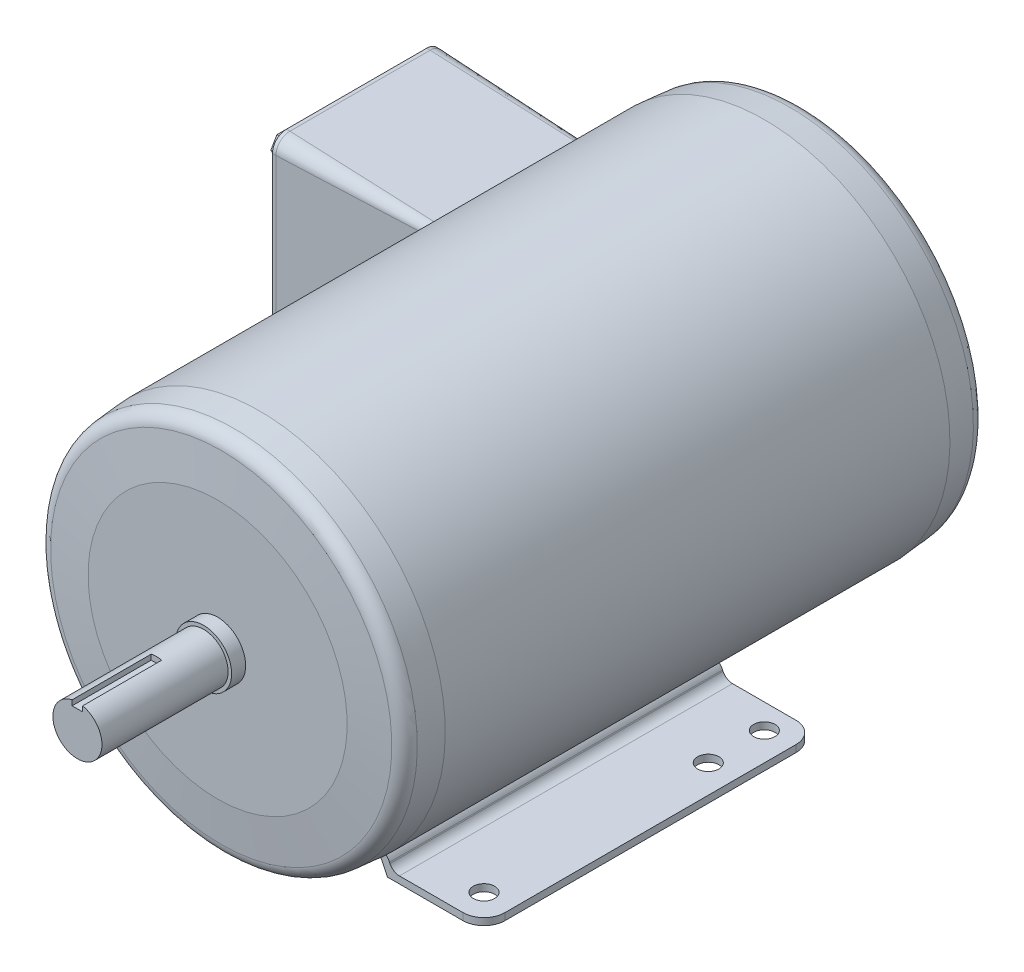
SolidWorks part; units mm, degrees
ref_plane "Front Plane" through (0, 0, 0) normal (0, 0, 1) x (1, 0, 0)
ref_plane "Top Plane" through (0, 0, 0) normal (0, 1, 0) x (1, 0, 0)
ref_plane "Right Plane" through (0, 0, 0) normal (1, 0, 0) x (0, 0, -1)
sketch "Sketch1" plane through (0, 0, 0) normal (0, 0, 1) x (1, 0, 0)
  line L0 (-82.55, -88.9) -> (-38.1, -88.9)
  line L1 (-38.1, -88.9) -> (-38.1, -85.725)
  line L2 (-38.1, -85.725) -> (-82.55, -85.725)
  line L3 (-82.55, -85.725) -> (-82.55, -88.9)
  line L4 (0, 0) -> (0, -88.9) construction
  line L5 (82.55, -85.725) -> (82.55, -88.9)
  line L6 (38.1, -85.725) -> (82.55, -85.725)
  line L7 (38.1, -88.9) -> (38.1, -85.725)
  line L8 (82.55, -88.9) -> (38.1, -88.9)
  line L9 (-69.85, -88.9) -> (-69.85, -85.725) construction
  line L10 (69.85, -88.9) -> (69.85, -85.725) construction
  line L11 (0, 0) -> (0, 84.074) construction
  line L12 (-2.3876, 8.4709) -> (2.3876, 8.4709) construction
  line L13 (-2.3876, 8.4709) -> (-2.3876, 10.853) construction
  line L14 (2.3876, 8.4709) -> (2.3876, 10.853) construction
  line L15 (0, 0) -> (84.074, 0) construction
  line L16 (0, 0) -> (-142.494, 0) construction
  line L17 (-142.494, 50.8) -> (-142.494, -50.8) construction
  line L18 (-142.494, 0) -> (-115.824, 0) construction
  line L19 (-115.824, 0) -> (-115.824, -50.8) construction
  line L20 (-142.494, -50.8) -> (-89.154, -50.8) construction
  line L22 (0, 0) -> (84.074, 0) construction
  line L23 (84.074, 12.7) -> (84.074, -25.4) construction
  circle A0 centre (0, 0) radius 84.074
  circle A1 centre (0, 0) radius 11.1125
  point P19 (0, 11.1125)
  dimension "D1" = 25.4
  dimension "P" = 168.148
  dimension "U" = 22.225
  dimension "A" = 165.1
  dimension "D" = 88.9
  dimension "E" = 69.85
  dimension "2E" = 139.7
  dimension "G" = 3.175
  dimension "J" = 44.45
  dimension "O" = 172.974
  dimension "R" = 19.5834
  dimension "S" = 4.7752
  dimension "U-R" = 2.6416
  dimension "AB" = 142.494
  dimension "AE" = 88.9
  dimension "AF" = 50.8
  dimension "AC" = 115.824
  dimension "OL" = 84.074
  dimension "D2" = 12.7
sketch "Sketch2" plane through (0, 0, 0) normal (1, 0, 0) x (0, 0, -1)
  line L0 (0, 0) -> (330.2, 0) construction
  line L1 (101.6, -88.9) -> (252.476, -88.9) construction
  line L3 (252.476, -85.725) -> (101.6, -85.725) construction
  line L4 (101.6, -88.9) -> (127, -88.9)
  line L5 (101.6, -88.9) -> (101.6, -85.725)
  line L6 (101.6, -85.725) -> (127, -85.725)
  line L7 (127, -88.9) -> (127, -85.725)
  line L8 (203.2, -88.9) -> (203.2, -85.725)
  line L9 (252.476, -88.9) -> (203.2, -88.9)
  line L10 (252.476, -85.725) -> (203.2, -85.725)
  line L11 (252.476, -88.9) -> (252.476, -85.725)
  line L12 (114.3, -88.9) -> (114.3, -85.725) construction
  line L13 (215.9, -88.9) -> (215.9, -85.725) construction
  line L14 (109.474, -88.9) -> (109.474, -85.725) construction
  line L15 (119.126, -88.9) -> (119.126, -85.725) construction
  line L16 (0, 11.1125) -> (0, 0) construction
  line L18 (241.3, -88.9) -> (241.3, -85.725) construction
  line L19 (165.1, 0) -> (165.1, -88.9) construction
  line L20 (203.2, -88.9) -> (127, -88.9) construction
  point P5 (35.814, 0)
  point P7 (264.16, 0)
  point P23 (63.5, 0)
  point P24 (57.15, 0)
  point P25 (50.8, 0)
  dimension "D1" = 66.04
  dimension "B" = 150.876
  dimension "C" = 330.2
  dimension "2F" = 101.6
  dimension "H" = 9.652
  dimension "K" = 25.4
  dimension "N" = 63.5
  dimension "W" = 6.35
  dimension "N-W" = 57.15
  dimension "V" = 50.8
  dimension "BA" = 57.15
  dimension "ES" = 35.814
  dimension "BS" = 149.86
  dimension "EV" = 12.7
  dimension "D5" = 12.7
  dimension "D6" = 127
sketch "Sketch3" plane through (0, 0, 0) normal (1, 0, 0) x (0, 0, -1)
  line L0 (0, 0) -> (330.2, 0) construction
  line L1 (82.55, 0) -> (311.15, 0)
  line L2 (82.55, 0) -> (82.55, 84.074) construction
  line L3 (82.55, 84.074) -> (311.15, 84.074)
  line L4 (311.15, 0) -> (311.15, 84.074) construction
  line L5 (82.55, 84.074) -> (70.9004, 83.0548)
  line L6 (65.128, 77.2824) -> (63.5, 58.674)
  line L7 (196.85, 84.074) -> (196.85, 0) construction
  line L8 (330.2, 0) -> (330.2, 58.674)
  line L9 (311.15, 84.074) -> (322.7996, 83.0548)
  line L10 (82.55, 0) -> (63.5, 0)
  line L11 (311.15, 0) -> (330.2, 0)
  line L12 (63.5, 0) -> (63.5, 58.674)
  line L13 (328.572, 77.2824) -> (330.2, 58.674)
  line L14 (0, 0) -> (63.5, 0) construction
  arc A0 (70.9004, 83.0548) -> (65.128, 77.2824) centre (71.4539, 76.729) ccw
  arc A1 (322.7996, 83.0548) -> (328.572, 77.2824) centre (322.2461, 76.729) cw
  dimension "D3" = 6.35
  dimension "D1" = 5
  dimension "D2" = 19.05
  dimension "D4" = 5
  dimension "D5" = 25.4
revolve "Revolve1" add sketch "Sketch3" angle 360 about L1
sketch "Sketch4" plane through (0, 0, 0) normal (1, 0, 0) x (0, 0, -1)
  line L0 (57.15, 11.1125) -> (57.15, 12.7)
  line L1 (0, 0) -> (63.5, 0)
  line L2 (0, 0) -> (0, 11.1125)
  line L3 (0, 11.1125) -> (57.15, 11.1125)
  line L4 (63.5, 0) -> (63.5, 12.7)
  line L5 (57.15, 12.7) -> (63.5, 12.7)
  line L6 (63.5, 58.674) -> (63.5, -58.674) construction
  line L7 (57.15, 11.1125) -> (57.15, 0) construction
  line L8 (12.7, 11.1125) -> (12.7, 0) construction
  dimension "D1" = 1.5875
  dimension "D2" = 12.7
revolve "Revolve2" add sketch "Sketch4" angle 360 about L1
sketch "Sketch5" plane through (0, 0, 0) normal (0, 0, 1) x (1, 0, 0)
  line L1 (-2.3876, 13.2461) -> (2.3876, 13.2461)
  line L2 (-2.3876, 13.2461) -> (-2.3876, 8.4709)
  line L3 (-2.3876, 8.4709) -> (2.3876, 8.4709)
  line L4 (2.3876, 13.2461) -> (2.3876, 8.4709)
extrude "Cut-Extrude1" cut sketch "Sketch5" against normal up to vertex (35.814 mm away) up to point (0, 0, -35.814)
ref_plane "Plane1" through (0, -88.9, 0) normal (0, 1, 0) x (-1, 0, 0)
sketch "Sketch6" plane through (0, -88.9, 0) normal (0, 1, 0) x (-1, 0, 0)
  line L0 (0, 0) -> (0, -330.2) construction
  line L1 (73.025, -101.6) -> (38.1, -101.6)
  line L2 (82.55, -111.125) -> (82.55, -242.951)
  line L3 (-73.025, -252.476) -> (-38.1, -252.476)
  line L4 (38.1, -101.6) -> (38.1, -252.476)
  line L5 (-38.1, -101.6) -> (-38.1, -252.476)
  line L6 (-82.55, -111.125) -> (-82.55, -242.951)
  line L7 (73.025, -252.476) -> (38.1, -252.476)
  line L8 (-73.025, -101.6) -> (-38.1, -101.6)
  line L9 (-58.674, -330.2) -> (58.674, -330.2) construction
  line L10 (69.85, -114.3) -> (69.85, -215.9) construction
  line L11 (69.85, -215.9) -> (69.85, -241.3) construction
  arc A0 (-82.55, -242.951) -> (-73.025, -252.476) centre (-73.025, -242.951) ccw
  arc A1 (-73.025, -101.6) -> (-82.55, -111.125) centre (-73.025, -111.125) ccw
  circle A2 centre (69.85, -114.3) radius 4.826
  circle A4 centre (69.85, -215.9) radius 4.826
  circle A5 centre (69.85, -241.3) radius 4.826
  circle A6 centre (-69.85, -241.3) radius 4.826
  circle A7 centre (-69.85, -215.9) radius 4.826
  arc A8 (73.025, -101.6) -> (82.55, -111.125) centre (73.025, -111.125) cw
  circle A9 centre (-69.85, -114.3) radius 4.826
  arc A11 (82.55, -242.951) -> (73.025, -252.476) centre (73.025, -242.951) cw
  point P30 (69.85, -109.474)
  dimension "D2" = 9.525
extrude "Boss-Extrude1" add sketch "Sketch6" along normal up to vertex (3.175 mm away) separate body up to point (-82.55, -85.725, 0)
sketch "Sketch7" plane through (0, -85.725, 0) normal (0, 1, 0) x (1, 0, 0)
  line L0 (38.1, 252.476) -> (38.1, 101.6) construction
  line L9 (0, 0) -> (0, 101.6) construction
  line L10 (0, 0) -> (0, 330.2) construction
  line L11 (-41.275, 252.476) -> (-41.275, 101.6)
  line L17 (41.275, 101.6) -> (-41.275, 101.6)
  line L19 (-41.275, 252.476) -> (41.275, 252.476)
  line L26 (41.275, 252.476) -> (41.275, 101.6)
  point P2 (-34.6506, 200.025)
  point P3 (-39.6875, 214.4395)
  point P6 (39.6875, 214.4395)
  point P8 (41.275, 212.725)
  point P12 (50.8, 203.2)
  point P14 (84.1375, 189.0395)
  point P16 (84.1375, 122.3645)
  point P18 (50.8, 127)
  point P31 (39.6875, 96.9645)
  point P32 (-39.6875, 96.9645)
  point P33 (-34.6506, 124.462)
  point P35 (-42.5881, 132.3995)
  point P36 (-84.1375, 122.3645)
  point P37 (-84.1375, 189.0395)
  point P38 (-42.5881, 192.0875)
  dimension "D2" = 3.175
extrude "Boss-Extrude2" add sketch "Sketch7" against normal blind 1.5875
ref_plane "Plane2" through (0, 0, -165.1) normal (0, 0, 1) x (1, 0, 0)
sketch "Sketch8" plane through (0, 0, -101.6) normal (0, 0, 1) x (1, 0, 0)
  line L0 (0, 0) -> (36.4726, -75.7508) construction
  line L1 (36.4726, -75.7508) -> (41.275, -85.725)
  line L2 (41.275, -85.725) -> (-41.275, -85.725)
  line L3 (0, -88.9) -> (0, 0) construction
  line L4 (-36.4726, -75.7508) -> (-41.275, -85.725)
  circle A0 centre (0, 0) radius 84.074 construction
  circle A1 centre (0, 0) radius 84.074 construction
  arc A2 (36.4726, -75.7508) -> (-36.4726, -75.7508) centre (0, 0) cw
extrude "Boss-Extrude4" add sketch "Sketch8" against normal up to surface (150.876 mm away) up to face at (0, -87.7094, -252.476)
sketch "Sketch9" plane through (0, 0, -101.6) normal (0, 0, 1) x (1, 0, 0)
  line L0 (38.8644, -88.9) -> (34.6207, -80.0862)
  line L1 (0, 0) -> (0, -87.3125) construction
  line L2 (-38.1, -87.3125) -> (38.1, -87.3125) construction
  line L3 (41.275, -85.725) -> (36.4726, -75.7508) construction
  line L4 (38.1, -88.9) -> (73.025, -88.9) construction
  line L5 (38.8644, -88.9) -> (-38.8644, -88.9)
  line L7 (-38.8644, -88.9) -> (-34.6207, -80.0862)
  arc A3 (-37.85, -78.6115) -> (37.85, -78.6115) centre (0, 0) ccw
  arc A4 (-34.6207, -80.0862) -> (34.6207, -80.0862) centre (0, 0) ccw
  dimension "D1" = 3.175
extrude "Cut-Extrude4" cut sketch "Sketch9" against normal up to surface (150.876 mm away) up to face at (2.2456, -86.0792, -252.476)
fillet "Fillet1" radius 4.7625 4 edges at (-34.6207, -80.0862, -177.038) (34.6207, -80.0862, -177.038)
fillet "Fillet3" radius 7.9375 2 edges at (36.4726, -75.7508, -177.038) (-36.4726, -75.7508, -177.038)
ref_plane "Plane3" through (-142.494, 0, 0) normal (1, 0, 0) x (0, 0, -1)
combine bodies "Combine1" operation type add bodies to combine 104 133
sketch "Sketch10" plane through (-142.494, 0, 0) normal (1, 0, 0) x (0, 0, -1)
  line L0 (264.16, -50.8) -> (264.16, 0) construction
  line L1 (295.91, 50.8) -> (232.41, 50.8)
  line L2 (302.26, 44.45) -> (302.26, -44.45)
  line L3 (295.91, -50.8) -> (232.41, -50.8)
  line L4 (226.06, 44.45) -> (226.06, -44.45)
  line L5 (264.16, -50.8) -> (264.16, 50.8) construction
  line L6 (302.26, 0) -> (226.06, 0) construction
  arc A0 (295.91, 50.8) -> (302.26, 44.45) centre (295.91, 44.45) cw
  arc A1 (232.41, 50.8) -> (226.06, 44.45) centre (232.41, 44.45) ccw
  arc A2 (232.41, -50.8) -> (226.06, -44.45) centre (232.41, -44.45) cw
  arc A3 (302.26, -44.45) -> (295.91, -50.8) centre (295.91, -44.45) cw
  dimension "D1" = 6.35
  dimension "D2" = 76.2
extrude "Boss-Extrude6" add sketch "Sketch10" along normal blind 6.35 separate body
sketch "Sketch11" plane through (-136.144, 0, 0) normal (1, 0, 0) x (0, 0, -1)
  line L4 (295.91, 50.8) -> (232.41, 50.8)
  line L5 (226.06, 44.45) -> (226.06, -44.45)
  line L6 (232.41, -50.8) -> (295.91, -50.8)
  line L7 (302.26, -44.45) -> (302.26, 44.45)
  line L8 (295.91, 50.8) -> (232.41, 50.8)
  line L9 (226.06, 44.45) -> (226.06, -44.45)
  line L10 (232.41, -50.8) -> (295.91, -50.8)
  line L11 (302.26, -44.45) -> (302.26, 44.45)
  arc A4 (302.26, 44.45) -> (295.91, 50.8) centre (295.91, 44.45) ccw
  arc A5 (232.41, 50.8) -> (226.06, 44.45) centre (232.41, 44.45) ccw
  arc A6 (226.06, -44.45) -> (232.41, -50.8) centre (232.41, -44.45) ccw
  arc A7 (295.91, -50.8) -> (302.26, -44.45) centre (295.91, -44.45) ccw
  arc A8 (302.26, 44.45) -> (295.91, 50.8) centre (295.91, 44.45) ccw
  arc A9 (232.41, 50.8) -> (226.06, 44.45) centre (232.41, 44.45) ccw
  arc A10 (226.06, -44.45) -> (232.41, -50.8) centre (232.41, -44.45) ccw
  arc A11 (295.91, -50.8) -> (302.26, -44.45) centre (295.91, -44.45) ccw
  dimension "D1" = 0
extrude "Boss-Extrude7" add sketch "Sketch11" along normal up to next draft 2.5 separate body
shell "Shell1" thickness 4.7625 removed face at (-73.0966, 0, -264.16)
sketch "Sketch12" plane through (0.4076, -44.838, 0) normal (0.0436, -0.999, 0) x (0.999, 0.0436, 0)
  line L0 (1.5486, -264.16) -> (-105.205, -264.16) construction
  line L1 (-116.381, -252.984) -> (-116.381, 0) construction
  line L2 (-105.205, -264.16) -> (-116.381, -264.16) construction
  line L3 (-116.381, -264.16) -> (-116.381, -252.984) construction
  line L4 (-116.381, -264.16) -> (-124.2836, -256.2574) construction
  circle A0 centre (-116.381, -264.16) radius 11.176
  dimension "D1" = 45
  dimension "AA" = 22.352
extrude "Cut-Extrude2" cut sketch "Sketch12" against normal up to next (4.7625 mm away)
sketch "Sketch13" plane through (-142.494, 0, 0) normal (-1, 0, 0) x (0, 0, 1)
  line L0 (-292.735, 41.275) -> (-292.735, 50.8) construction
  line L1 (-292.735, 41.275) -> (-235.585, 41.275) construction
  line L2 (-292.735, 41.275) -> (-292.735, -41.275) construction
  line L3 (-292.735, -41.275) -> (-235.585, -41.275) construction
  line L4 (-302.26, 44.45) -> (-302.26, -44.45)
  line L5 (-295.91, -50.8) -> (-232.41, -50.8)
  line L6 (-226.06, -44.45) -> (-226.06, 44.45)
  line L7 (-232.41, 50.8) -> (-295.91, 50.8)
  line L8 (-302.26, 44.45) -> (-302.26, -44.45)
  line L9 (-295.91, -50.8) -> (-232.41, -50.8)
  line L10 (-226.06, -44.45) -> (-226.06, 44.45)
  line L11 (-232.41, 50.8) -> (-295.91, 50.8)
  line L12 (-235.585, 41.275) -> (-235.585, -41.275) construction
  line L13 (-287.2357, 41.275) -> (-289.9854, 46.0375)
  line L14 (-289.9854, 46.0375) -> (-295.4846, 46.0375)
  line L15 (-295.4846, 46.0375) -> (-298.2343, 41.275)
  line L16 (-298.2343, 41.275) -> (-295.4846, 36.5125)
  line L17 (-295.4846, 36.5125) -> (-289.9854, 36.5125)
  line L18 (-289.9854, 36.5125) -> (-287.2357, 41.275)
  line L19 (-241.0843, 41.275) -> (-238.3346, 36.5125)
  line L20 (-238.3346, 36.5125) -> (-232.8354, 36.5125)
  line L21 (-232.8354, 36.5125) -> (-230.0857, 41.275)
  line L22 (-230.0857, 41.275) -> (-232.8354, 46.0375)
  line L23 (-232.8354, 46.0375) -> (-238.3346, 46.0375)
  line L24 (-238.3346, 46.0375) -> (-241.0843, 41.275)
  line L25 (-287.2357, -41.275) -> (-289.9854, -36.5125)
  line L26 (-289.9854, -36.5125) -> (-295.4846, -36.5125)
  line L27 (-295.4846, -36.5125) -> (-298.2343, -41.275)
  line L28 (-298.2343, -41.275) -> (-295.4846, -46.0375)
  line L29 (-295.4846, -46.0375) -> (-289.9854, -46.0375)
  line L30 (-289.9854, -46.0375) -> (-287.2357, -41.275)
  line L31 (-241.0843, -41.275) -> (-238.3346, -46.0375)
  line L32 (-238.3346, -46.0375) -> (-232.8354, -46.0375)
  line L33 (-232.8354, -46.0375) -> (-230.0857, -41.275)
  line L34 (-230.0857, -41.275) -> (-232.8354, -36.5125)
  line L35 (-232.8354, -36.5125) -> (-238.3346, -36.5125)
  line L36 (-238.3346, -36.5125) -> (-241.0843, -41.275)
  line L37 (-292.735, 41.275) -> (-302.26, 41.275) construction
  line L38 (-292.735, -41.275) -> (-292.735, -50.8) construction
  line L39 (-235.585, 41.275) -> (-226.06, 41.275) construction
  circle A0 centre (-292.735, 41.275) radius 4.7625 construction
  circle A1 centre (-235.585, 41.275) radius 4.7625 construction
  circle A2 centre (-292.735, -41.275) radius 4.7625 construction
  circle A3 centre (-235.585, -41.275) radius 4.7625 construction
  arc A4 (-295.91, 50.8) -> (-302.26, 44.45) centre (-295.91, 44.45) ccw
  arc A5 (-302.26, -44.45) -> (-295.91, -50.8) centre (-295.91, -44.45) ccw
  arc A6 (-232.41, -50.8) -> (-226.06, -44.45) centre (-232.41, -44.45) ccw
  arc A7 (-226.06, 44.45) -> (-232.41, 50.8) centre (-232.41, 44.45) ccw
  arc A8 (-295.91, 50.8) -> (-302.26, 44.45) centre (-295.91, 44.45) ccw
  arc A9 (-302.26, -44.45) -> (-295.91, -50.8) centre (-295.91, -44.45) ccw
  arc A10 (-232.41, -50.8) -> (-226.06, -44.45) centre (-232.41, -44.45) ccw
  arc A11 (-226.06, 44.45) -> (-232.41, 50.8) centre (-232.41, 44.45) ccw
  dimension "D2" = 9.525
  dimension "D3" = 9.525
  dimension "D1" = 0
extrude "Cut-Extrude3" cut sketch "Sketch13" against normal blind 4.7625
combine bodies "Combine2" operation type add bodies to combine 116 120 117
sketch "Sketch15" plane through (0, -88.9, 0) normal (0, -1, 0) x (1, 0, 0)
  line L0 (-82.55, -177.038) -> (82.55, -177.038) construction
  line L1 (-82.55, -242.951) -> (-82.55, -111.125) construction
  line L2 (82.55, -111.125) -> (82.55, -242.951) construction
  line L4 (0, -102.6757) -> (0, -253.1845) construction
  point P6 (0, -177.038)
